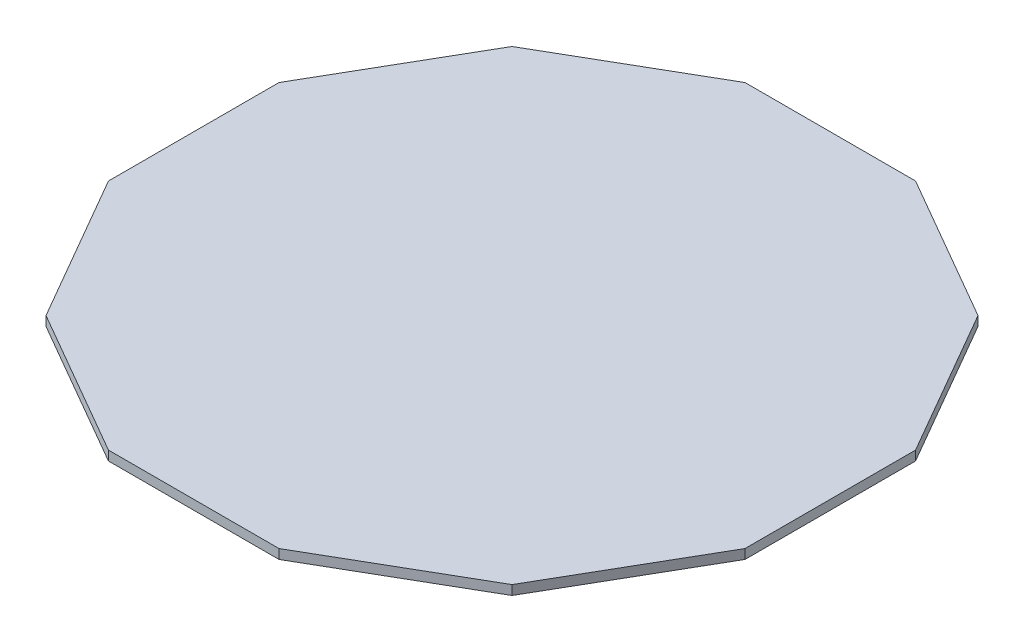
SolidWorks part; units mm, degrees
material "ABS PC"
ref_plane "Front Plane" through (0, 0, 0) normal (0, 0, 1) x (1, 0, 0)
ref_plane "Top Plane" through (0, 0, 0) normal (0, 1, 0) x (1, 0, 0)
ref_plane "Right Plane" through (0, 0, 0) normal (1, 0, 0) x (0, 0, -1)
sketch "Sketch1" plane through (0, 0, 0) normal (0, 1, 0) x (1, 0, 0)
  line L0 (26.296, 98.1381) -> (-26.296, 98.1381)
  line L1 (-26.296, 98.1381) -> (-71.842, 71.842)
  line L2 (-71.842, 71.842) -> (-98.1381, 26.296)
  line L3 (-98.1381, 26.296) -> (-98.1381, -26.296)
  line L4 (-98.1381, -26.296) -> (-71.842, -71.842)
  line L5 (-71.842, -71.842) -> (-26.296, -98.1381)
  line L6 (-26.296, -98.1381) -> (26.296, -98.1381)
  line L7 (26.296, -98.1381) -> (71.842, -71.842)
  line L8 (71.842, -71.842) -> (98.1381, -26.296)
  line L9 (98.1381, -26.296) -> (98.1381, 26.296)
  line L10 (98.1381, 26.296) -> (71.842, 71.842)
  line L11 (71.842, 71.842) -> (26.296, 98.1381)
  circle A0 centre (0, 0) radius 101.6
  dimension "D1" = 203.2
extrude "Boss-Extrude1" add sketch "Sketch1" against normal blind 2.921 contours L10 L11 L0 L1 L2 L3 L4 L5 L6 L7 L8 L9 region at (0, 0, 0)
